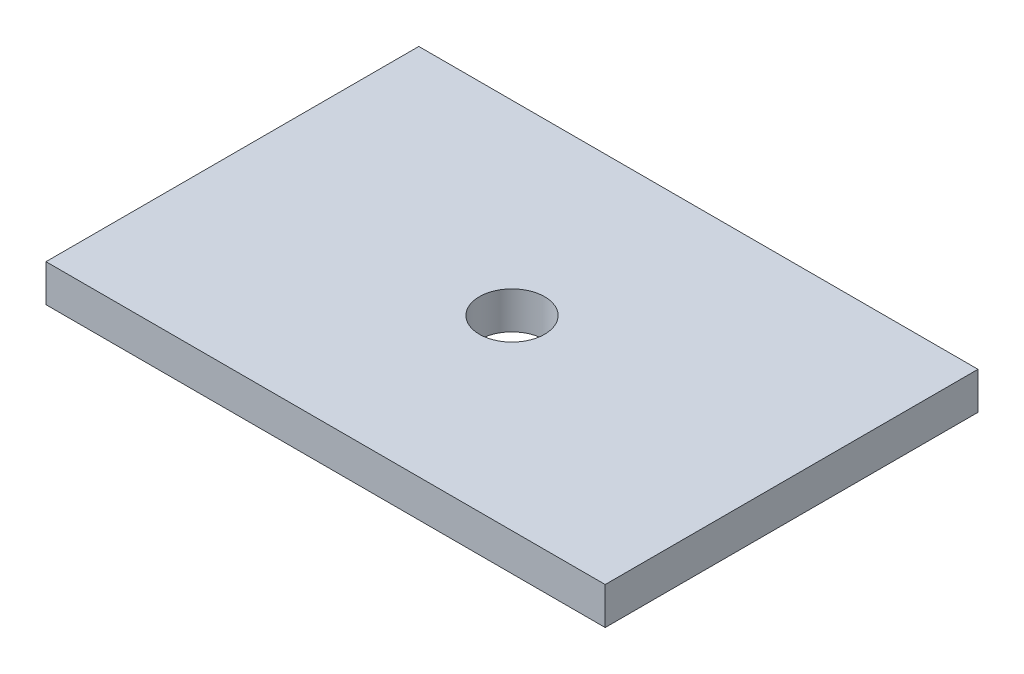
SolidWorks part; units mm, degrees
ref_plane "Front Plane" through (0, 0, 0) normal (0, 0, 1) x (1, 0, 0)
ref_plane "Top Plane" through (0, 0, 0) normal (0, 1, 0) x (1, 0, 0)
ref_plane "Right Plane" through (0, 0, 0) normal (1, 0, 0) x (0, 0, -1)
ref_axis "X-Axis" through (-88.99, 0, 0) along (1, 0, 0)
ref_axis "Y-Axis" through (0, 55, 0) along (0, -1, 0)
ref_axis "Z-Axis" through (0, 0, -88.99) along (0, 0, 1)
sketch "Sketch1" plane through (0, 0, 0) normal (0, 1, 0) x (1, 0, 0)
  line L1 (-15, -10) -> (15, -10)
  line L2 (-15, -10) -> (-15, 10)
  line L3 (-15, 10) -> (15, 10)
  line L4 (15, -10) -> (15, 10)
  line L5 (-15, -10) -> (15, 10) construction
  line L6 (-15, 10) -> (15, -10) construction
  point P0 (0, 0)
  dimension "D1" = 30
  dimension "D2" = 20
extrude "Boss-Extrude1" add sketch "Sketch1" along normal blind 2
sketch "Sketch2" plane through (0, 2, 0) normal (0, 1, 0) x (1, 0, 0)
  circle A0 centre (0, 0) radius 1.75
  dimension "D1" = 3.5
extrude "Cut-Extrude1" cut sketch "Sketch2" against normal through all
